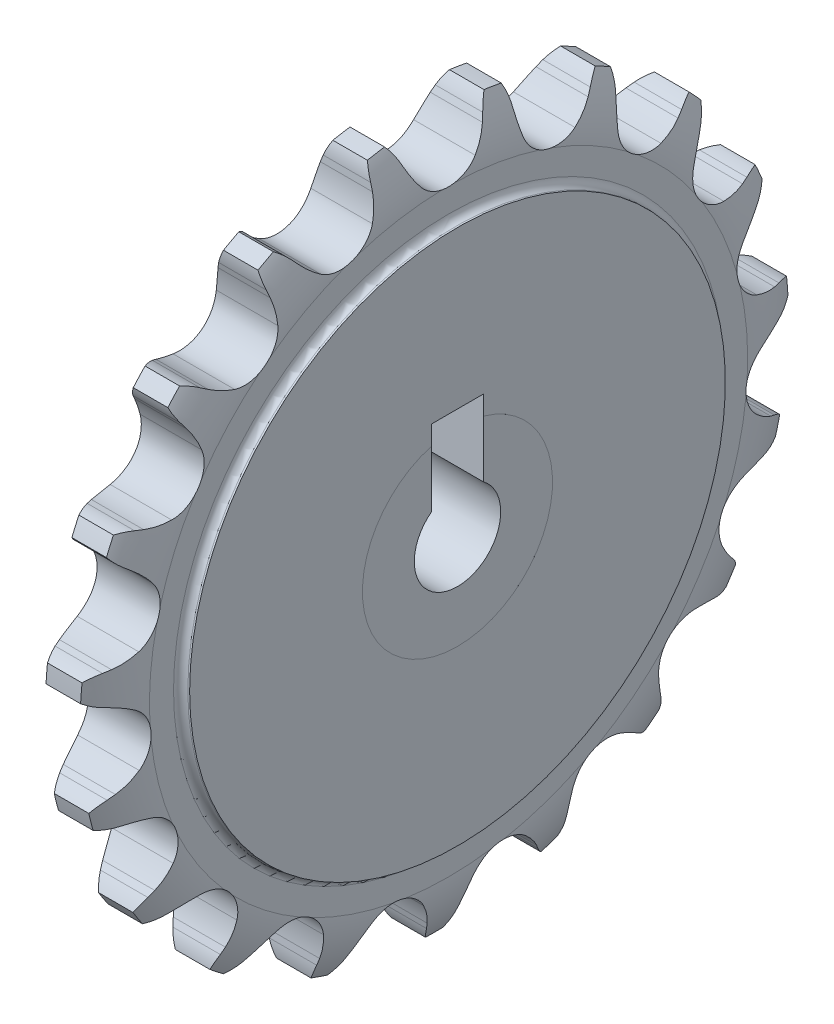
SolidWorks part; units mm, degrees
ref_plane "前视基准面" through (0, 0, 0) normal (0, 0, 1) x (1, 0, 0)
ref_plane "上视基准面" through (0, 0, 0) normal (0, 1, 0) x (1, 0, 0)
ref_plane "右视基准面" through (0, 0, 0) normal (1, 0, 0) x (0, 0, -1)
sketch "草图1" plane through (0, 0, 0) normal (0, 0, 1) x (1, 0, 0)
  line L0 (-6.35, 0) -> (6.35, 0) construction
  line L1 (-4.6852, 10) -> (-4.6852, 31)
  line L2 (-4.6852, 31) -> (-4.4782, 31)
  line L3 (-3.6502, 31.8279) -> (-3.6502, 34.6196)
  line L4 (-1.9992, 41) -> (1.9992, 41)
  line L5 (3.6502, 34.6196) -> (3.6502, 31.8279)
  line L6 (4.4782, 31) -> (4.6852, 31)
  line L7 (4.6852, 31) -> (4.6852, 10)
  line L8 (4.6852, 10) -> (-4.6852, 10)
  line L9 (0, 0) -> (0, 41) construction
  line L10 (-3.0556, 38.5796) -> (3.0556, 38.5796) construction
  line L11 (-3.0556, -38.5796) -> (3.0556, -38.5796) construction
  line L12 (6.35, 0) -> (25.35, 0) construction
  line L13 (-3.6502, 34.6196) -> (3.7984, 34.6196) construction
  line L14 (-3.6502, -34.6196) -> (3.7984, -34.6196) construction
  line L15 (25.35, 0) -> (33.27, 0) construction
  line L16 (33.27, 0) -> (45.34, 0) construction
  line L17 (45.34, 0) -> (53.19, 0) construction
  line L18 (53.19, 0) -> (67.57, 0) construction
  arc A0 (-1.9992, 41) -> (-3.6502, 34.6196) centre (9.0492, 34.7373) ccw
  arc A1 (1.9992, 41) -> (3.6502, 34.6196) centre (-9.0492, 34.7373) cw
  arc A2 (3.6502, 31.8279) -> (4.4782, 31) centre (4.4782, 31.8279) ccw
  arc A3 (-4.4782, 31) -> (-3.6502, 31.8279) centre (-4.4782, 31.8279) ccw
  point P30 (3.6502, 31)
  point P33 (-3.6502, 31)
  dimension "D1" = 3.6196
  dimension "rx" = 12.7
  dimension "D3" = 0.8279
  dimension "d" = 77.1593
  dimension "p" = 12.7
  dimension "z" = 19
  dimension "da" = 82
  dimension "df" = 69.2393
  dimension "dr" = 7.92
  dimension "dk" = 20
  dimension "dg" = 62
  dimension "h" = 12.07
  dimension "bf1" = 7.3005
  dimension "b1" = 7.85
  dimension "ba" = 1.651
  dimension "D2" = 1.0349
  dimension "pt" = 14.38
revolve "旋转1" add sketch "草图1" angle 360 about L0
sketch "草图2" plane through (0, 0, 0) normal (1, 0, 0) x (0, 0, -1)
  line L0 (0, 0) -> (0, 41) construction
  line L1 (0, 0) -> (-6.7484, 40.4408) construction
  line L2 (0, 0) -> (-13.3127, 38.7785) construction
  line L3 (3.1687, 36.0899) -> (3.1879, 36.0748) construction
  line L4 (4.5522, 38.4265) -> (-4.9821, 42.4942) construction
  line L5 (0, 0) -> (6.7484, 40.4408) construction
  line L6 (4.5522, 38.4265) -> (4.8587, 39.1448)
  line L7 (-4.5522, 38.4265) -> (-4.8587, 39.1448)
  circle A0 centre (0, 0) radius 41 construction
  arc A1 (3.1687, 36.0899) -> (-3.1687, 36.0899) centre (0, 38.5796) cw
  arc A2 (3.1687, 36.0899) -> (4.5522, 38.4265) centre (-4.9821, 42.4942) ccw
  arc A3 (5.7509, 40.5947) -> (4.8587, 39.1448) centre (10.1556, 36.885) ccw
  arc A4 (-3.1687, 36.0899) -> (-4.5522, 38.4265) centre (4.9821, 42.4942) cw
  arc A5 (-5.7509, 40.5947) -> (-4.8587, 39.1448) centre (-10.1556, 36.885) cw
  arc A7 (5.7509, 40.5947) -> (-5.7509, 40.5947) centre (0, 0) ccw
  dimension "r1" = 4.0298
  dimension "r3" = 5.7588
  dimension "D1" = 18.947
  dimension "D2" = 9.474
  dimension "α/2" = 51.842
  dimension "M" = 4.9821
  dimension "T" = 3.9146
  dimension "β" = 15.053
  dimension "γ/2" = 13.632
  dimension "bc" = 0.781
extrude "切除-拉伸1" cut sketch "草图2" against normal mid plane 9.3703
pattern_circular "阵列(圆周)1" count 19 over 360 about axis through (-6.35, 0, 0) along (1, 0, 0) of "切除-拉伸1"
sketch "草图3" plane through (0, 0, 0) normal (0, 0, 1) x (1, 0, 0)
  line L0 (4.6852, 10) -> (10.3148, 10)
  line L3 (10.3148, 10) -> (10.3148, 18.9049)
  line L4 (10.3148, 18.9049) -> (4.6852, 18.9049)
  line L5 (4.6852, 18.9049) -> (4.6852, 10)
  line L6 (0, 0) -> (4.8, 0) construction
  line L8 (-4.6852, 31) -> (-4.6852, -31) construction
  dimension "h" = 8.9049
  dimension "K" = 4.8
  dimension "L" = 15
revolve "旋转2" [suppressed] add sketch "草图3" angle 360 about L6
sketch "草图4" plane through (-4.6852, 0, 0) normal (-1, 0, 0) x (0, 0, 1)
  line L1 (-3, 9.5394) -> (3, 9.5394)
  line L2 (-3, 9.5394) -> (-3, 12.8)
  line L3 (-3, 12.8) -> (3, 12.8)
  line L4 (3, 9.5394) -> (3, 12.8)
  circle A0 centre (0, 0) radius 10 construction
  point P6 (0.2, 12.8)
  dimension "D1" = 12.8
  dimension "键槽宽度" = 6
  dimension "t1" = 2.8
extrude "切除-拉伸2" cut sketch "草图4" against normal through all
chamfer "倒角1" distance 1 angle 45 1 edges at (-4.6852, -10, 0)
chamfer "倒角2" distance 1 angle 45 1 edges at (4.6852, -10, 0)
chamfer "倒角3" [suppressed] distance 1 angle 45
sketch "草图5" plane through (0, 0, 0) normal (1, 0, 0) x (0, 0, -1)
  circle A0 centre (0, 0) radius 11
  circle A1 centre (0, 0) radius 5
  dimension "D1" = 10
extrude "凸台-拉伸1" add sketch "草图5" along normal mid plane 9.37
sketch "草图6" plane through (4.685, 0, 0) normal (1, 0, 0) x (0, 0, -1)
  line L0 (-3, 12.8) -> (-3, 1.6519)
  line L1 (-3, 1.6519) -> (3, 4)
  line L2 (3, 4) -> (3, 12.8)
  line L3 (3, 12.8) -> (-3, 12.8)
  circle A0 centre (0, 0) radius 5 construction
extrude "切除-拉伸3" cut sketch "草图6" against normal blind 12.37
